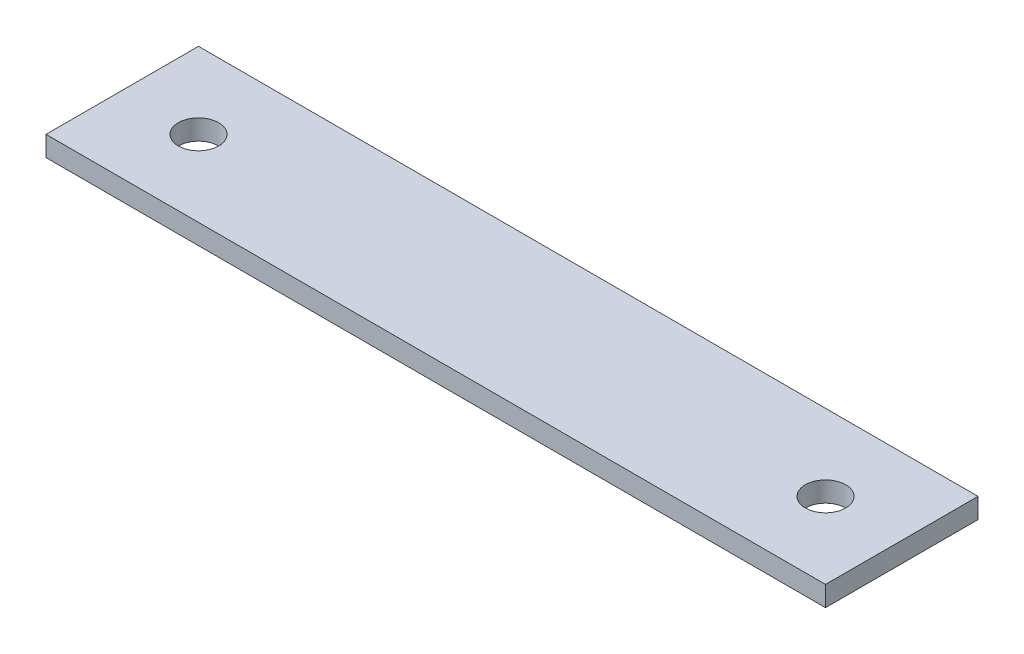
SolidWorks part; units mm, degrees
ref_plane "Front Plane" through (0, 0, 0) normal (0, 0, 1) x (1, 0, 0)
ref_plane "Top Plane" through (0, 0, 0) normal (0, 1, 0) x (1, 0, 0)
ref_plane "Right Plane" through (0, 0, 0) normal (1, 0, 0) x (0, 0, -1)
sketch "Sketch1" plane through (0, 0, 0) normal (0, 1, 0) x (1, 0, 0)
  line L0 (-24.672, 0) -> (24.672, 0) construction
  line L1 (30.672, -6) -> (-30.672, -6)
  line L2 (30.672, -6) -> (30.672, 6)
  line L3 (30.672, 6) -> (-30.672, 6)
  line L4 (-30.672, -6) -> (-30.672, 6)
  line L5 (30.672, -6) -> (-30.672, 6) construction
  line L6 (30.672, 6) -> (-30.672, -6) construction
  circle A0 centre (-24.672, 0) radius 1.5875
  circle A1 centre (24.672, 0) radius 1.5875
  circle A2 centre (-24.672, 0) radius 5 construction
  point P0 (0, 0)
  point P8 (0, 0)
  dimension "D1" = 3.175
  dimension "D4" = 10
  dimension "D2" = 49.344
  dimension "D3" = 12
  dimension "D5" = 6
extrude "Boss-Extrude1" add sketch "Sketch1" along normal mid plane 1.5875
